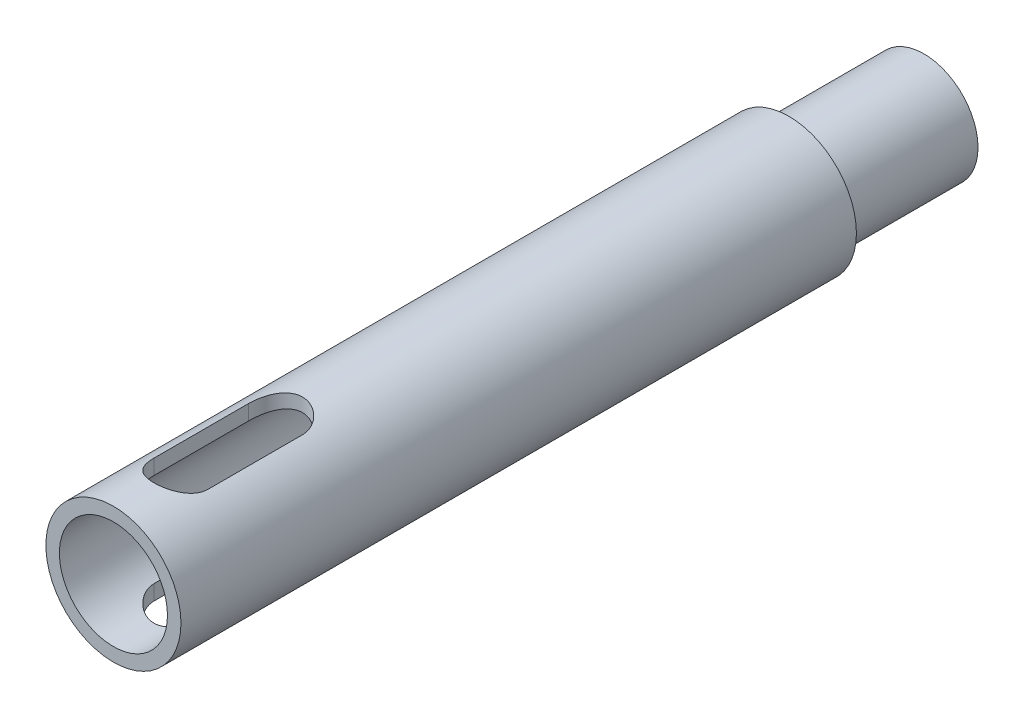
SolidWorks part; units mm, degrees
ref_plane "Front Plane" through (0, 0, 0) normal (0, 0, 1) x (1, 0, 0)
ref_plane "Top Plane" through (0, 0, 0) normal (0, 1, 0) x (1, 0, 0)
ref_plane "Right Plane" through (0, 0, 0) normal (1, 0, 0) x (0, 0, -1)
sketch "Sketch1" plane through (0, 0, 0) normal (0, 0, 1) x (1, 0, 0)
  circle A0 centre (0, 0) radius 5
  circle A1 centre (0, 0) radius 4
  dimension "D1" = 10
  dimension "D2" = 8
extrude "Boss-Extrude1" add sketch "Sketch1" along normal blind 60 contours A1 | A0 A1 region at (-4.8586, 0, 0) region at (0, 0, 0)
extrude "Cut-Extrude1" cut sketch "Sketch1<4>" along normal blind 10
sketch "Sketch1<4>" plane through (0, 0, 0) normal (0, 0, 1) x (1, 0, 0) same geometry as "Sketch1"
extrude "Cut-Extrude2" cut sketch "Sketch1<5>" along normal blind 20 from offset 40 contours A1 region at (0, 0, 0)
sketch "Sketch1<5>" plane through (0, 0, 0) normal (0, 0, 1) x (1, 0, 0) same geometry as "Sketch1"
sketch "Sketch2" plane through (0, 0, 0) normal (0, 1, 0) x (1, 0, 0)
  line L0 (0, -48) -> (0, -55) construction
  line L1 (2, -48) -> (2, -55)
  line L2 (-2, -48) -> (-2, -55)
  line L3 (-5, -60) -> (5, -60) construction
  arc A0 (2, -48) -> (-2, -48) centre (0, -48) ccw
  arc A1 (-2, -55) -> (2, -55) centre (0, -55) ccw
  point P3 (0, -51.5)
  dimension "D1" = 2
  dimension "D2" = 7
  dimension "D3" = 5
extrude "Cut-Extrude3" cut sketch "Sketch2" against normal through all both and the other way through all
